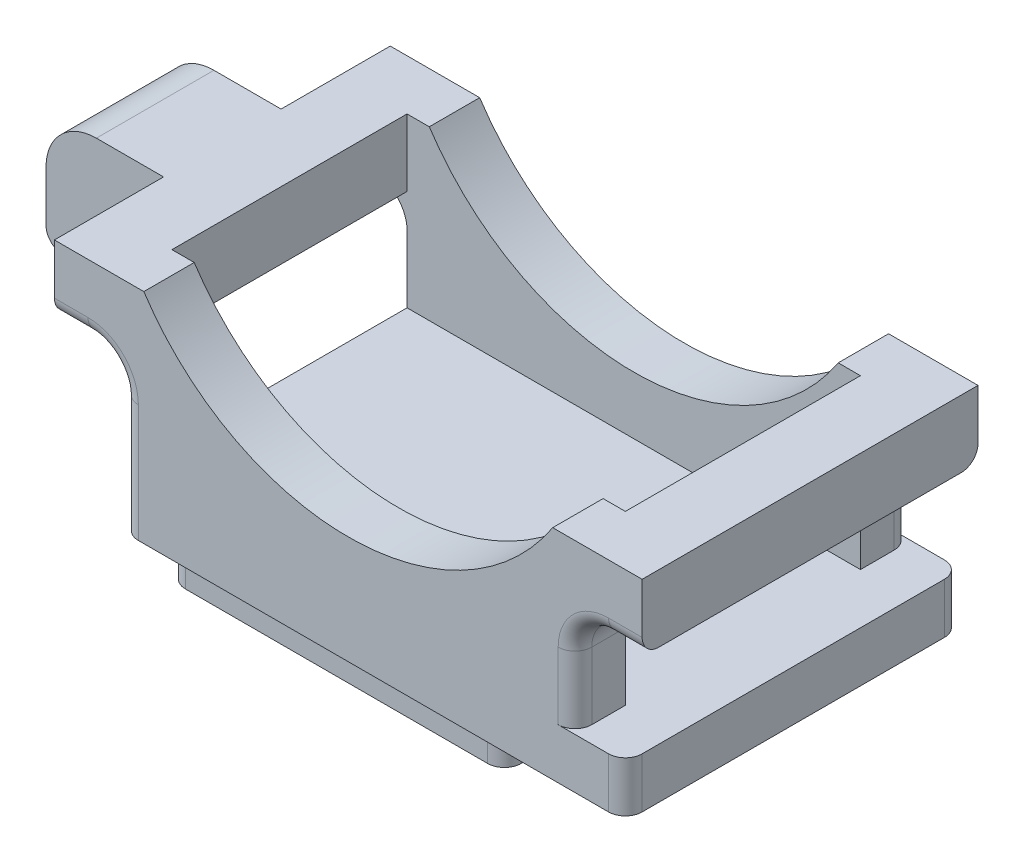
SolidWorks part; units mm, degrees
ref_plane "Front" through (0, 0, 0) normal (0, 0, 1) x (1, 0, 0)
ref_plane "Top" through (0, 0, 0) normal (0, 1, 0) x (1, 0, 0)
ref_plane "Right" through (0, 0, 0) normal (1, 0, 0) x (0, 0, -1)
sketch "Sketch1" plane through (0, 0, 0) normal (0, 1, 0) x (1, 0, 0)
  line L1 (0, 0) -> (20, 0)
  line L2 (0, 0) -> (0, -14.4)
  line L3 (0, -14.4) -> (20, -14.4)
  line L4 (20, 0) -> (20, -14.4)
  dimension "D1" = 20
  dimension "D2" = 14.4
extrude "Boss-Extrude1" add sketch "Sketch1" along normal blind 1.8
sketch "Sketch2" plane through (0, 1.8, 0) normal (0, 1, 0) x (1, 0, 0)
  line L0 (20, -14.4) -> (20, 0) construction
  line L1 (20, -12.2) -> (0, -12.2)
  line L2 (20, -12.2) -> (20, -2.2)
  line L3 (20, -2.2) -> (0, -2.2)
  line L4 (0, -12.2) -> (0, -2.2)
  line L5 (0, 0) -> (0, -14.4) construction
  line L6 (0, -14.4) -> (20, -14.4) construction
  line L7 (20, 0) -> (0, 0) construction
  dimension "D1" = 2.2
  dimension "D2" = 2.2
extrude "Boss-Extrude2" add sketch "Sketch2" along normal blind 2.1
sketch "Sketch3" plane through (0, 3.9, 0) normal (0, 1, 0) x (1, 0, 0)
  line L0 (20, -2.2) -> (0, -2.2) construction
  line L1 (30, 2.8) -> (0, 2.8)
  line L2 (30, 2.8) -> (30, -17.2)
  line L3 (30, -17.2) -> (0, -17.2)
  line L4 (0, 2.8) -> (0, -17.2)
  line L5 (0, -12.2) -> (20, -12.2) construction
  line L6 (20, -12.2) -> (20, -2.2) construction
  dimension "D1" = 5
  dimension "D2" = 5
  dimension "D3" = 10
  dimension "D4" = 20
extrude "Boss-Extrude3" add sketch "Sketch3" along normal blind 3
sketch "Sketch4" plane through (0, 3.9, 0) normal (0, -1, 0) x (-1, 0, 0)
  line L0 (0, 2.8) -> (0, -2.2) construction
  line L1 (-27, -14.7) -> (-29, -14.7)
  line L2 (-27, -14.7) -> (-27, 0.3)
  line L3 (-27, 0.3) -> (-29, 0.3)
  line L4 (-29, -14.7) -> (-29, 0.3)
  line L6 (-30, 2.8) -> (0, 2.8) construction
  dimension "D1" = 27
  dimension "D2" = 2
  dimension "D3" = 15
  dimension "D4" = 2.5
extrude "Boss-Extrude4" add sketch "Sketch4" along normal blind 0.8
fillet "Fillet1" radius 1.5 1 edges at (27, 3.1, 7.2)
sketch "Sketch5" plane through (0, 6.9, 0) normal (0, 1, 0) x (1, 0, 0)
  line L0 (0, 2.8) -> (0, -17.2) construction
  line L1 (0, -14.2) -> (30, -14.2)
  line L2 (0, -14.2) -> (0, -17.2)
  line L3 (0, -17.2) -> (30, -17.2)
  line L4 (30, -14.2) -> (30, -17.2)
  line L5 (30, -17.2) -> (30, 2.8) construction
  line L6 (0, 2.8) -> (30, 2.8)
  line L7 (0, 2.8) -> (0, -0.2)
  line L8 (0, -0.2) -> (30, -0.2)
  line L9 (30, 2.8) -> (30, -0.2)
  line L10 (27, 2.8) -> (27, -0.2)
  line L11 (27, -14.2) -> (27, -17.2)
  line M4 (0, 2.8) -> (0, -17.2)
  line M5 (0, -17.2) -> (30, -17.2)
  dimension "D1" = 14
  dimension "D2" = 3
  dimension "D3" = 27
  dimension "D4" = 27
extrude "Boss-Extrude6" add sketch "Sketch5" along normal blind 10 contours L10 L6 L8 M4 | L11 L1 M4 M5 region at (13.5, 6.9, 15.7) region at (13.5, 6.9, -1.3)
sketch "Sketch6" plane through (0, 0, 17.2) normal (0, 0, 1) x (1, 0, 0)
  line L0 (0, 16.9) -> (27, 16.9) construction
  line L1 (0, 16.9) -> (0, 3.9) construction
  line L2 (1.3251, 16.9) -> (25.6749, 16.9)
  arc A0 (1.3251, 16.9) -> (25.6749, 16.9) centre (13.5, 24.9) ccw
  dimension "D1" = 8
  dimension "D2" = 13.5
extrude "Cut-Extrude1" cut sketch "Sketch6" against normal through all
sketch "Sketch7" plane through (27, 0, 0) normal (1, 0, 0) x (0, 0, -1)
  line L0 (-17.2, 16.9) -> (-17.2, 6.9) construction
  line L1 (-17.2, 12.9) -> (2.8, 12.9)
  line L2 (-17.2, 12.9) -> (-17.2, 16.9)
  line L3 (-17.2, 16.9) -> (2.8, 16.9)
  line L4 (2.8, 12.9) -> (2.8, 16.9)
  line L5 (2.8, 16.9) -> (2.8, 6.9) construction
  line L6 (-14.2, 16.9) -> (-17.2, 16.9) construction
  dimension "D1" = 0
  dimension "D2" = 6
  dimension "D3" = 0
extrude "Boss-Extrude7" add sketch "Sketch7" along normal blind 4
sketch "Sketch8" plane through (0, 0, 0) normal (-1, 0, 0) x (0, 0, 1)
  line L0 (17.2, 16.9) -> (17.2, 3.9) construction
  line L1 (-2.8, 16.9) -> (17.2, 16.9)
  line L2 (-2.8, 16.9) -> (-2.8, 12.9)
  line L3 (-2.8, 12.9) -> (17.2, 12.9)
  line L4 (17.2, 16.9) -> (17.2, 12.9)
  line L5 (0.2, 6.9) -> (14.2, 6.9) construction
  dimension "D1" = 6
extrude "Boss-Extrude8" add sketch "Sketch8" along normal blind 4
fillet "Fillet3" radius 2 4 edges at (27, 12.9, -1.3) (27, 12.9, 15.7) (0, 12.9, 15.7) (0, 12.9, -1.3)
fillet "Fillet2" radius 1 12 edges at (0, 7.4, 17.2) (0, 7.4, -2.8) (30, 5.4, -2.8) (30, 5.4, 17.2) (20, 0.9, 14.4) (20, 0.9, 0) (0, 0.9, 14.4) (0, 0.9, 0) (-3, 12.9, 17.2) (-0.5858, 12.3142, 17.2) (-3, 12.9, -2.8) (-0.5858, 12.3142, -2.8)
fillet "Fillet4" radius 1 6 edges at (30, 12.9, 17.2) (27.5858, 12.3142, 17.2) (30, 12.9, -2.8) (27.5858, 12.3142, -2.8) (27, 8.9, 17.2) (27, 8.9, -2.8)
sketch "Sketch10" plane through (-4, 0, 0) normal (-1, 0, 0) x (0, 0, 1)
  line L0 (17.2, 16.9) -> (-2.8, 16.9) construction
  line L1 (3.7, 16.9) -> (10.7, 16.9)
  line L2 (3.7, 16.9) -> (3.7, 12.9)
  line L3 (3.7, 12.9) -> (10.7, 12.9)
  line L4 (10.7, 16.9) -> (10.7, 12.9)
  line L5 (-1.8, 12.9) -> (16.2, 12.9) construction
  line L6 (17.2, 13.9) -> (17.2, 16.9) construction
  dimension "D1" = 7
  dimension "D2" = 6.5
extrude "Boss-Extrude10" add sketch "Sketch10" along normal blind 7
sketch "Sketch11" plane through (0, 12.9, 0) normal (0, -1, 0) x (-1, 0, 0)
  line L0 (11, -10.7) -> (4, -10.7) construction
  line L1 (11, -3.7) -> (8, -3.7)
  line L2 (11, -3.7) -> (11, -10.7)
  line L3 (11, -10.7) -> (8, -10.7)
  line L4 (8, -3.7) -> (8, -10.7)
  dimension "D1" = 3
extrude "Boss-Extrude11" add sketch "Sketch11" along normal blind 3
fillet "Fillet5" radius 2 1 edges at (-8, 12.9, 7.2)
fillet "Fillet6" radius 1 2 edges at (-11, 9.9, 7.2) (-8, 9.9, 7.2)
fillet "Fillet7" radius 3 1 edges at (-11, 16.9, 7.2)
equation "\"D4@Sketch4\"=(\"D4@Sketch3\"-\"D3@Sketch4\")/2"
equation "\"D2@Sketch5\"=(\"D4@Sketch3\"-\"D1@Sketch5\")/2"
equation "\"D2@Sketch6\"=\"D4@Sketch5\"/2"
equation "\"D2@Sketch10\"=(\"D4@Sketch3\"-\"D1@Sketch10\")/2"
